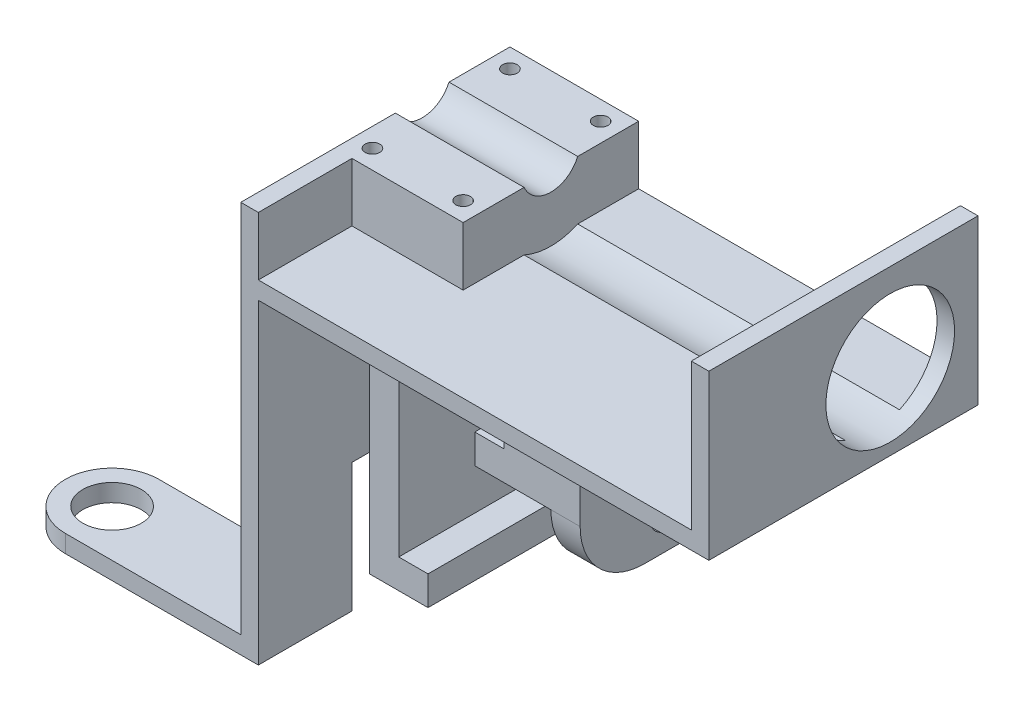
SolidWorks part; units mm, degrees
material "Custom Plastic"
ref_plane "Front Plane" through (0, 0, 0) normal (0, 0, 1) x (1, 0, 0)
ref_plane "Top Plane" through (0, 0, 0) normal (0, 1, 0) x (1, 0, 0)
ref_plane "Right Plane" through (0, 0, 0) normal (1, 0, 0) x (0, 0, -1)
sketch "Sketch1" plane through (0, 0, 0) normal (0, 0, 1) x (1, 0, 0)
  line L0 (-13, -38) -> (-23, -38)
  line L1 (-23, -38) -> (-23, -2)
  line L2 (-23, -2) -> (-25, 0)
  line L4 (-25, 0) -> (-26, 0)
  line L5 (-26, 0) -> (-26, -23)
  line L6 (-26, -23) -> (-29, -23)
  line L7 (-29, -23) -> (-29, 22)
  line L8 (-29, 22) -> (-7, 22)
  line L9 (-7, 22) -> (-7, 12)
  line L10 (-7, 12) -> (48, 12)
  line L11 (48, 12) -> (48, 37)
  line L12 (48, 37) -> (51, 37)
  line L13 (51, 37) -> (51, 9)
  line L14 (51, 9) -> (18, 5)
  line L15 (18, 5) -> (13, 0)
  line L16 (13, 0) -> (13, -45)
  line L17 (13, -45) -> (8, -45)
  line L18 (8, -45) -> (8, -13)
  line L19 (8, -13) -> (-5, -13)
  line L20 (-5, -13) -> (-5, -8)
  line L21 (-5, -8) -> (0, -8)
  line L22 (0, -8) -> (0, 0)
  line L23 (0, 0) -> (-18, 0)
  line L24 (-18, 0) -> (-18, -33)
  line L25 (-18, -33) -> (-13, -33)
  line L26 (-13, -33) -> (-13, -38)
  dimension "D1" = 5
  dimension "D2" = 3
  dimension "D3" = 18
  dimension "D4" = 8
  dimension "D5" = 5
  dimension "D6" = 5
  dimension "D7" = 8
  dimension "D8" = 33
  dimension "D9" = 13
  dimension "D10" = 5
  dimension "D11" = 5
  dimension "D12" = 12
  dimension "D13" = 80
  dimension "D14" = 3
  dimension "D15" = 1
  dimension "D16" = 22
  dimension "D17" = 10
  dimension "D18" = 45
  dimension "D19" = 5
  dimension "D20" = 45
  dimension "D21" = 3
  dimension "D22" = 15
  dimension "D23" = 25
  dimension "D24" = 45
  dimension "D25" = 3
extrude "Boss-Extrude1" add sketch "Sketch1" along normal blind 30
sketch "Sketch2" plane through (51, 0, 0) normal (1, 0, 0) x (0, 0, -1)
  line L0 (-30, 37) -> (0, 37) construction
  line L1 (-30, 9) -> (-30, 37) construction
  line L2 (0, 9) -> (0, 37) construction
  circle A0 centre (-15, 22) radius 11
  circle A1 centre (-15, 22) radius 15 construction
  dimension "D1" = 22
extrude "Cut-Extrude1" cut sketch "Sketch2" against normal up to surface (58 mm away) up to face at (-7, 17, 15)
sketch "Sketch3" plane through (-7, 0, 0) normal (1, 0, 0) x (0, 0, -1)
  line L0 (-30, 22) -> (0, 22) construction
  circle A0 centre (-15, 24) radius 5
  point P5 (-15, 22)
  dimension "D1" = 10
  dimension "D2" = 2
extrude "Cut-Extrude2" cut sketch "Sketch3" against normal up to surface (22 mm away) up to face at (-29, -0.5, 15)
sketch "Sketch5" plane through (0, -23, 0) normal (0, -1, 0) x (1, 0, 0)
  line L0 (-29, 0) -> (-33.2, 0)
  line L1 (-29, 30) -> (-29, 0) construction
  line L2 (-29, 0) -> (-26, 0) construction
  line L3 (-33.2, 0) -> (-33.2, 1.7)
  line L4 (-33.2, 1.7) -> (-32, 1.7)
  line L5 (-32, 1.7) -> (-32, 1.2)
  line L6 (-32, 1.2) -> (-29, 1.2)
  line L7 (-29, 1.2) -> (-29, 0)
  line L8 (-29, 14.2801) -> (-29, 13.0801)
  line L9 (-29, 13.0801) -> (-33.2, 13.0801)
  line L10 (-33.2, 13.0801) -> (-33.2, 14.7801)
  line L11 (-33.2, 14.7801) -> (-32, 14.7801)
  line L12 (-32, 14.7801) -> (-32, 14.2801)
  line L13 (-32, 14.2801) -> (-29, 14.2801)
  line L14 (-29, 27.3601) -> (-29, 26.1601)
  line L15 (-29, 26.1601) -> (-33.2, 26.1601)
  line L16 (-33.2, 26.1601) -> (-33.2, 27.8601)
  line L17 (-33.2, 27.8601) -> (-32, 27.8601)
  line L18 (-32, 27.8601) -> (-32, 27.3601)
  line L19 (-32, 27.3601) -> (-29, 27.3601)
  dimension "D1" = 3
  dimension "D2" = 1.2
  dimension "D3" = 1.2
  dimension "D4" = 0.5
  dimension "D5" = 3
extrude "Boss-Extrude2" add sketch "Sketch5" against normal blind 5
extrude "Boss-Extrude3" add sketch "Sketch5<2>" along normal blind 5 from offset 20 offset against normal yes
sketch "Sketch5<2>" plane through (0, -23, 0) normal (0, -1, 0) x (1, 0, 0) same geometry as "Sketch5"
sketch "Sketch6" plane through (0, -23, 0) normal (0, -1, 0) x (1, 0, 0)
  line L0 (-29, 3.2) -> (-29, 4.4)
  line L1 (-29, 13.0801) -> (-29, 1.2) construction
  line L2 (-29, 4.4) -> (-33.2, 4.4)
  line L3 (-33.2, 4.4) -> (-33.2, 2.7)
  line L4 (-33.2, 2.7) -> (-32, 2.7)
  line L5 (-32, 2.7) -> (-32, 3.2)
  line L6 (-32, 3.2) -> (-29, 3.2)
  line L7 (-32, 1.2) -> (-32, 1.7) construction
  line L8 (-29, 1.2) -> (-32, 1.2) construction
  line L9 (-32, 1.7) -> (-33.2, 1.7) construction
  line L10 (-33.2, 1.7) -> (-33.2, 0) construction
  line L11 (-33.2, 0) -> (-26, 0) construction
  line L12 (-32, 15.998) -> (-29, 15.998)
  line L13 (-29, 15.998) -> (-29, 17.198)
  line L14 (-29, 17.198) -> (-33.2, 17.198)
  line L15 (-33.2, 17.198) -> (-33.2, 15.498)
  line L16 (-33.2, 15.498) -> (-32, 15.498)
  line L17 (-32, 15.498) -> (-32, 15.998)
  line L18 (-32, 28.7959) -> (-29, 28.7959)
  line L19 (-29, 28.7959) -> (-29, 29.9959)
  line L20 (-29, 29.9959) -> (-33.2, 29.9959)
  line L21 (-33.2, 29.9959) -> (-33.2, 28.2959)
  line L22 (-33.2, 28.2959) -> (-32, 28.2959)
  line L23 (-32, 28.2959) -> (-32, 28.7959)
  dimension "D1" = 2
  dimension "D2" = 3
extrude "Boss-Extrude4" add sketch "Sketch6" against normal blind 5 from offset 8 offset against normal yes
extrude "Boss-Extrude5" add sketch "Sketch6<2>" along normal blind 5 from offset 30 offset against normal yes
sketch "Sketch6<2>" plane through (0, -23, 0) normal (0, -1, 0) x (1, 0, 0) same geometry as "Sketch6"
sketch "Sketch7" plane through (0, 0, 30) normal (0, 0, 1) x (1, 0, 0)
  line L0 (-67, -42) -> (-29, -42)
  line L1 (-29, -42) -> (-29, 22)
  line L2 (-29, 22) -> (-26, 22)
  line L3 (-26, 22) -> (-26, -45)
  line L4 (-26, -45) -> (-67, -45)
  line L5 (-67, -45) -> (-67, -42)
  line L9 (-18, 0) -> (0, 0) construction
  line L10 (-29, 22) -> (-29, -23) construction
  line L11 (-7, 22) -> (-29, 22) construction
  dimension "D1" = 3
  dimension "D2" = 3
  dimension "D3" = 38
  dimension "D4" = 45
extrude "Boss-Extrude6" add sketch "Sketch7" along normal blind 16
sketch "Sketch8" plane through (0, -42, 0) normal (0, 1, 0) x (1, 0, 0)
  line L0 (-29, -46) -> (-67, -46) construction
  line L1 (-67, -46) -> (-67, -30) construction
  line L2 (-29, -30) -> (-67, -30) construction
  line L3 (-59, -30) -> (-67, -30)
  line L4 (-67, -30) -> (-67, -46)
  line L5 (-67, -46) -> (-59, -46)
  circle A0 centre (-59, -38) radius 5
  arc A1 (-59, -30) -> (-59, -46) centre (-59, -38) ccw
  arc A2 (-59, -46) -> (-59, -30) centre (-59, -38) ccw construction
  line M3 (-29, -30) -> (-67, -30)
  line M4 (-67, -30) -> (-67, -46)
  line M5 (-67, -46) -> (-29, -46)
  dimension "D1" = 10
extrude "Cut-Extrude3" cut sketch "Sketch8" against normal up to surface (3 mm away) contours A1 L4 M5 | A0 | A1 M3 M4 region at (-65.2131, -42, 31.7869) region at (-65.2131, -42, 44.2131) region at (-59, -42, 38) up to face at (-46.5, -45, 38)
sketch "Sketch9" plane through (0, 0, 30) normal (0, 0, 1) x (1, 0, 0)
  line L1 (51, 9) -> (-26, 9)
  line L2 (51, 9) -> (51, 12)
  line L3 (51, 12) -> (-26, 12)
  line L4 (-26, 9) -> (-26, 12)
  line L5 (48, 12) -> (-7, 12) construction
  line L6 (-26, -45) -> (-26, 22) construction
extrude "Boss-Extrude7" add sketch "Sketch9" along normal blind 16
sketch "Sketch10" plane through (0, 0, 30) normal (0, 0, 1) x (1, 0, 0)
  line L4 (48, 12) -> (51, 12)
  line L5 (51, 12) -> (51, 37)
  line L6 (51, 37) -> (48, 37)
  line L7 (48, 37) -> (48, 12)
  line L8 (48, 12) -> (51, 12)
  line L9 (51, 12) -> (51, 37)
  line L10 (51, 37) -> (48, 37)
  line L11 (48, 37) -> (48, 12)
  dimension "D1" = 0
extrude "Boss-Extrude8" add sketch "Sketch10" along normal up to surface (16 mm away) up to face at (-17.8, -8.8, 46)
sketch "Sketch11" plane through (8, 0, 0) normal (-1, 0, 0) x (0, 0, 1)
  line L0 (30, -13) -> (0, -13) construction
  line L1 (11, -13) -> (19, -13) construction
  line L2 (11, -2) -> (19, -2)
  line L3 (11, -24) -> (19, -24)
  line L4 (0, -13) -> (0, -45)
  line L5 (0, -45) -> (30, -45)
  line L6 (30, -45) -> (30, -13)
  circle A0 centre (15, -18) radius 3
  arc A1 (11, -2) -> (11, -24) centre (11, -13) ccw
  arc A2 (19, -24) -> (19, -2) centre (19, -13) ccw
  point P4 (15, -13)
  point P9 (15, -13)
  point P14 (15, -21)
  line M2 (0, -13) -> (0, -45)
  line M3 (0, -45) -> (30, -45)
  line M4 (30, -45) -> (30, -13)
  dimension "D1" = 6
  dimension "D2" = 5
  dimension "D3" = 3
extrude "Cut-Extrude4" cut sketch "Sketch11" against normal up to surface (5 mm away) contours A0 | A2 L3 A1 M2 M3 M4 region at (8, -33.5132, 15) region at (8, -18, 15) up to face at (13, -22.5, 15)
sketch "Sketch12" plane through (0, 22, 0) normal (0, 1, 0) x (1, 0, 0)
  line L0 (-7, -10.4174) -> (-7, 0) construction
  line L1 (-7, 0) -> (-29, 0) construction
  line L2 (-7, -30) -> (-7, -19.5826) construction
  line L3 (-7, -30) -> (-26, -30) construction
  line L5 (-29, -10.4174) -> (-29, 0) construction
  line L6 (-29, -46) -> (-29, -19.5826) construction
  circle A0 centre (-10.25, -3.25) radius 1.25
  circle A1 centre (-10.25, -3.25) radius 3.25 construction
  circle A2 centre (-10.25, -26.75) radius 1.25
  circle A3 centre (-10.25, -26.75) radius 3.25 construction
  circle A6 centre (-25.75, -3.25) radius 1.25
  circle A7 centre (-25.75, -3.25) radius 3.25 construction
  circle A8 centre (-25.75, -26.75) radius 1.25
  circle A9 centre (-25.75, -26.75) radius 3.25 construction
  dimension "D1" = 2
  dimension "D2" = 2.5
  dimension "D4" = 2.5
  dimension "D8" = 2.5
  dimension "D10" = 2.5
  dimension "D3" = 2
  dimension "D7" = 2
  dimension "D9" = 2
extrude "Cut-Extrude5" cut sketch "Sketch12" against normal blind 12
